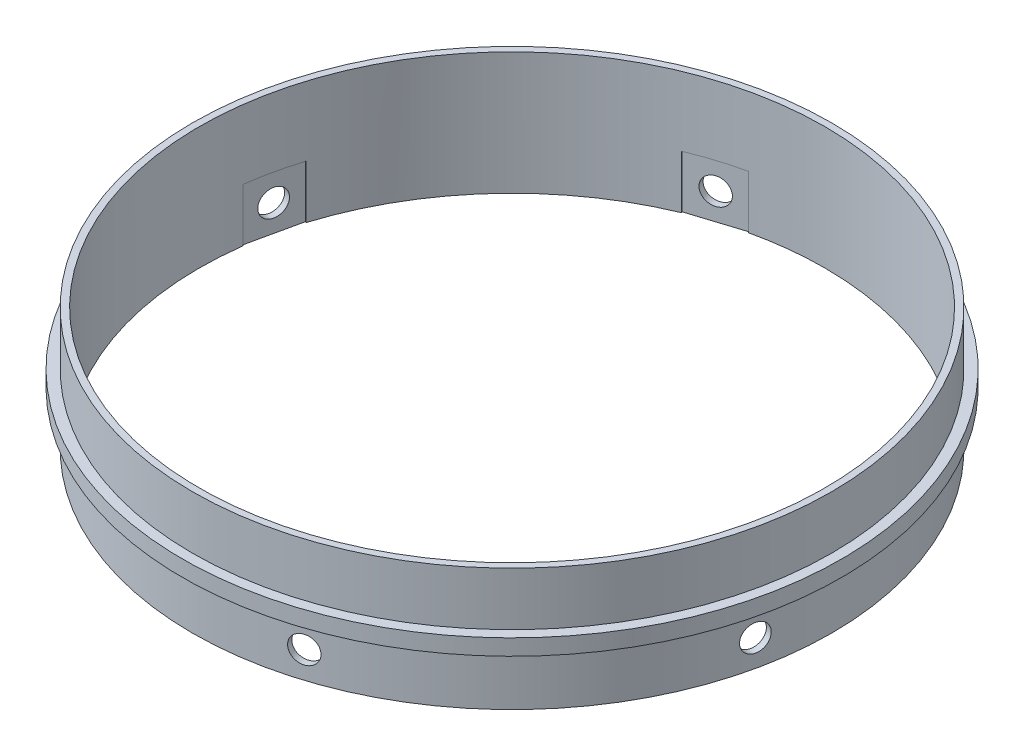
SolidWorks part; units mm, degrees
material "6061-T6 (SS)"
ref_plane "Front Plane" through (0, 0, 0) normal (0, 0, 1) x (1, 0, 0)
ref_plane "Top Plane" through (0, 0, 0) normal (0, 1, 0) x (1, 0, 0)
ref_plane "Right Plane" through (0, 0, 0) normal (1, 0, 0) x (0, 0, -1)
ref_axis "Axis1" through (0, -55, 0) along (0, 1, 0)
sketch "Sketch1" plane through (0, 0, 0) normal (0, 0, 1) x (1, 0, 0)
  line L0 (74.6125, 0) -> (74.6125, 29.21)
  line L1 (74.6125, 29.21) -> (76.2, 29.21)
  line L2 (76.2, 29.21) -> (76.2, 16.51)
  line L3 (76.2, 16.51) -> (78.5876, 16.51)
  line L4 (78.5876, 16.51) -> (78.5876, 12.7)
  line L5 (78.5876, 12.7) -> (76.2, 12.7)
  line L6 (76.2, 12.7) -> (76.2, 0)
  line L7 (76.2, 0) -> (74.6125, 0)
  line L8 (0, -55) -> (0, 55) construction
  line L9 (55, 0) -> (-55, 0) construction
  dimension "D1" = 1.5875
  dimension "D2" = 76.2
  dimension "D3" = 12.7
  dimension "D4" = 3.81
  dimension "D5" = 12.7
  dimension "D6" = 78.5876
revolve "Revolve1" add sketch "Sketch1" angle 360 about axis through (0, -55, 0) along (0, 1, 0)
hole_wizard "1/4 (0.25) Diameter Hole1" positions "3DSketch1" profile "Sketch2" hole size "1/4" standard "ANSI Inch" end condition up to next
sketch3d "3DSketch1"
  point P0 (23.046, 6.35, 72.6314)
  dimension "D1" = 6.35
sketch "Sketch2" plane through (23.046, 6.35, 72.6314) normal (0, 1, 0) x (0.9532, 0, -0.3024)
  line L0 (0, 0) -> (0, 181.6104)
  line L1 (0, 181.6104) -> (3.175, 181.6104)
  line L2 (3.175, 181.6104) -> (3.175, 0)
  line L5 (3.175, 0) -> (0, 0)
  line L11 (0, -6.35) -> (0, 107.95) construction
  dimension "Thru Hole Dia." = 6.35
  dimension "Thru Hole Depth" = 181.6104
pattern_circular "CirPattern1" count 6 over 360 about axis through (0, -55, 0) along (0, 1, 0) of "1/4 (0.25) Diameter Hole1"
ref_axis "Axis2" through (-71.3027, 6.35, -15.6713) along (-0.9767, 0, -0.2147)
ref_plane "Plane1" through (72.8732, 0, 16.0165) normal (-0.9767, 0, -0.2147) x (-0.2147, 0, 0.9767)
sketch "Sketch3" plane through (72.8732, 0, 16.0165) normal (-0.9767, 0, -0.2147) x (-0.2147, 0, 0.9767)
  line L0 (-74.6125, 0) -> (74.6125, 0) construction
  line L1 (-6.35, 0) -> (6.35, 0)
  line L2 (-6.35, 0) -> (-6.35, 12.7)
  line L3 (-6.35, 12.7) -> (6.35, 12.7)
  line L4 (6.35, 0) -> (6.35, 12.7)
  line L5 (-6.35, 0) -> (6.35, 12.7) construction
  line L6 (-6.35, 12.7) -> (6.35, 0) construction
  point P0 (0, 6.35)
  dimension "D1" = 12.7
extrude "Cut-Extrude4" cut sketch "Sketch3" against normal blind 0.0025 and the other way blind 2.54
pattern_circular "CirPattern2" count 6 over 360 about axis through (0, -55, 0) along (0, 1, 0) of "Cut-Extrude4"
